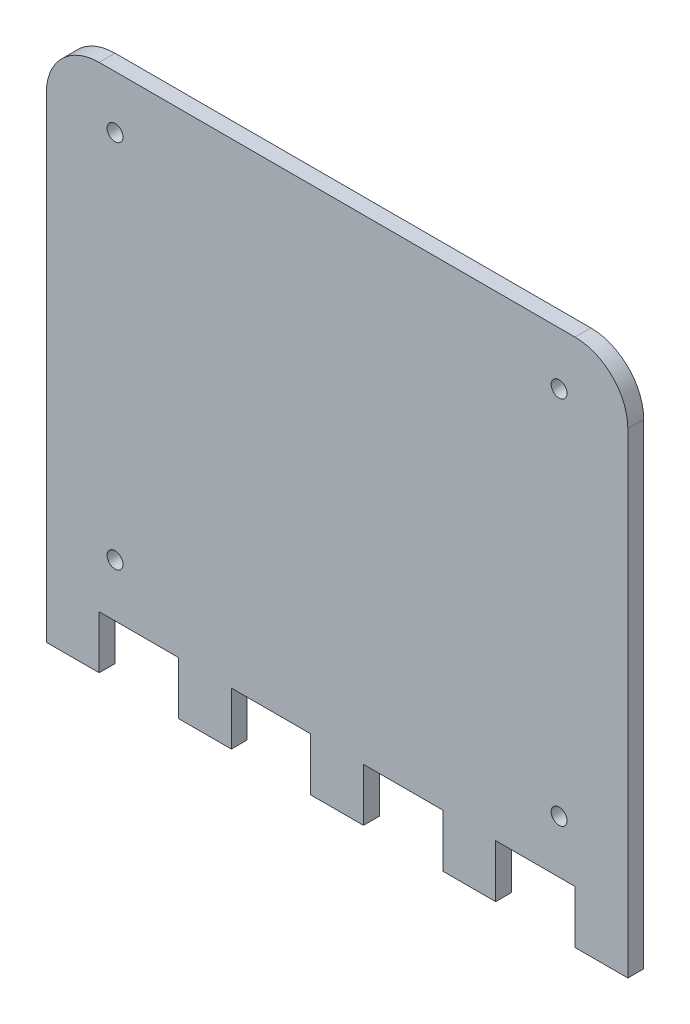
SolidWorks part; units mm, degrees
ref_plane "Спереди" through (0, 0, 0) normal (0, 0, 1) x (1, 0, 0)
ref_plane "Сверху" through (0, 0, 0) normal (0, 1, 0) x (1, 0, 0)
ref_plane "Справа" through (0, 0, 0) normal (1, 0, 0) x (0, 0, -1)
sketch "Эскиз1" plane through (0, 0, 0) normal (0, 0, 1) x (1, 0, 0)
  line L0 (-20, -45) -> (-20, -55)
  line L1 (45, -45) -> (30, -45)
  line L2 (55, -45) -> (55, 35)
  line L3 (45, 45) -> (-45, 45)
  line L4 (-55, -45) -> (-55, 35)
  line L5 (55, -45) -> (-55, 45) construction
  line L6 (55, 45) -> (-55, -45) construction
  line L12 (-55, -45) -> (-55, -55)
  line L13 (-55, -55) -> (-45, -55)
  line L14 (-45, -45) -> (-45, -55)
  line L15 (-30, -55) -> (-20, -55)
  line L16 (-30, -45) -> (-30, -55)
  line L17 (5, -45) -> (5, -55)
  line L18 (-5, -55) -> (5, -55)
  line L19 (-5, -45) -> (-5, -55)
  line L20 (30, -45) -> (30, -55)
  line L21 (20, -55) -> (30, -55)
  line L22 (20, -45) -> (20, -55)
  line L23 (55, -45) -> (55, -55)
  line L24 (45, -55) -> (55, -55)
  line L25 (45, -45) -> (45, -55)
  line L26 (-30, -45) -> (-45, -45)
  line L27 (-5, -45) -> (-20, -45)
  line L28 (20, -45) -> (5, -45)
  arc A0 (55, 35) -> (45, 45) centre (45, 35) ccw
  arc A1 (-45, 45) -> (-55, 35) centre (-45, 35) ccw
  point P0 (0, 0)
  dimension "D3" = 10
  dimension "D1" = 110
  dimension "D2" = 90
  dimension "D4" = 10
  dimension "D5" = 10
  dimension "D6" = 5
extrude "Бобышка-Вытянуть2" add sketch "Эскиз1" along normal mid plane 3
sketch "Эскиз2" plane through (0, 0, 1.5) normal (0, 0, 1) x (1, 0, 0)
  line L0 (55, -55) -> (55, 35) construction
  line L5 (45, 45) -> (-45, 45) construction
  line L6 (47, -40) -> (-47, -40) construction
  line L7 (47, -40) -> (47, 40) construction
  line L8 (47, 40) -> (-47, 40) construction
  line L9 (-47, -40) -> (-47, 40) construction
  line L10 (47, -40) -> (-47, 40) construction
  line L11 (47, 40) -> (-47, -40) construction
  point P0 (0, 0)
  point P5 (0, 0)
  dimension "D1" = 5
  dimension "D2" = 94
  dimension "D3" = 8
  dimension "D4" = 80
sketch "Эскиз3" plane through (0, 0, 1.5) normal (0, 0, 1) x (1, 0, 0)
  line L1 (47, 40) -> (-47, 40) construction
  line L3 (-47, -40) -> (-47, 40) construction
  line L4 (0, 0) -> (0, 22.2229) construction
  line L6 (0, 0) -> (-8.2285, 0) construction
  circle A0 centre (-42, 35) radius 1.5
  circle A1 centre (42, 35) radius 1.5
  circle A2 centre (42, -35) radius 1.5
  circle A3 centre (-42, -35) radius 1.5
  dimension "D1" = 5
  dimension "D2" = 5
extrude "Вырез-Вытянуть1" cut sketch "Эскиз3" against normal up to surface (3 mm away) up to face at (0, -33.9026, -1.5)
